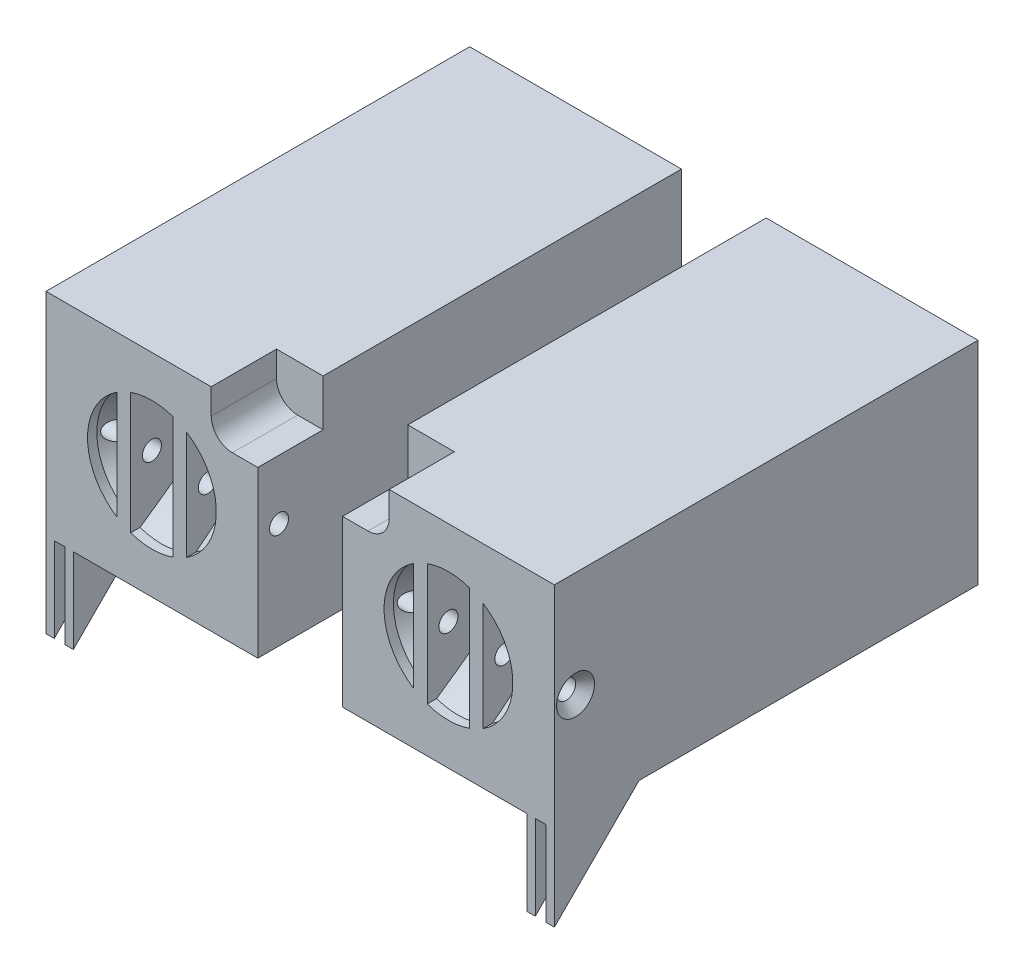
SolidWorks part; units mm, degrees
ref_plane "Alzado" through (0, 0, 0) normal (0, 0, 1) x (1, 0, 0)
ref_plane "Planta" through (0, 0, 0) normal (0, 1, 0) x (1, 0, 0)
ref_plane "Vista lateral" through (0, 0, 0) normal (1, 0, 0) x (0, 0, -1)
sketch "Croquis1" plane through (0, 0, 0) normal (0, 0, 1) x (1, 0, 0)
  line L1 (25, -25) -> (-25, -25)
  line L2 (25, -25) -> (25, 25)
  line L3 (25, 25) -> (-25, 25)
  line L4 (-25, -25) -> (-25, 25)
  line L5 (25, -25) -> (-25, 25) construction
  line L6 (25, 25) -> (-25, -25) construction
  circle A0 centre (0, 0) radius 2
  point P0 (0, 0)
  dimension "D3" = 4
  dimension "D1" = 50
  dimension "D2" = 50
extrude "Saliente-Extruir2" add sketch "Croquis1" along normal blind 100
ref_plane "Plano1" through (0, 0, 0) normal (1, 0, 0) x (0, 0, -1)
sketch "Croquis2" plane through (0, 0, 0) normal (1, 0, 0) x (0, 0, -1)
  line L1 (-100, 25) -> (-100, -25) construction
  line L4 (-100, 15.2) -> (-100, 0)
  line L6 (-97.8, 15.2) -> (-89.8, 10)
  line L7 (-100, 15.2) -> (-97.8, 15.2)
  line L8 (-89.8, 0) -> (-89.8, 10)
  line L9 (-100, 0) -> (-89.8, 0)
  dimension "D1" = 2.2
  dimension "D2" = 10.2
  dimension "D3" = 10
  dimension "D4" = 15.2
revolve "Cortar-Revolución1" cut sketch "Croquis2" angle 360 about L9
sketch "Croquis4" plane through (0, 0, 100) normal (0, 0, 1) x (1, 0, 0)
  line L0 (0, -0.44) -> (0, 0.44) construction
  line L1 (-8.2, 20) -> (-5, 20)
  line L2 (-8.2, 20) -> (-8.2, -20)
  line L3 (-8.2, -20) -> (-5, -20)
  line L4 (-5, 20) -> (-5, -20)
  line L5 (8.2, -20) -> (5, -20)
  line L6 (5, 20) -> (5, -20)
  line L7 (8.2, 20) -> (5, 20)
  line L8 (8.2, 20) -> (8.2, -20)
  point P6 (-5, 0)
  dimension "D1" = 3.2
  dimension "D2" = 5
  dimension "D3" = 40
extrude "Saliente-Extruir5" add sketch "Croquis4" along direction (0, 0, 1) on the side against the normal up to surface (10.2 mm away) up to face at (0, -2, 89.8)
sketch "Croquis8" plane through (0, 0, 89.8) normal (0, 0, 1) x (1, 0, 0)
  circle A0 centre (0, 0) radius 4
  dimension "D1" = 8
extrude "Cortar-Extruir3" cut sketch "Croquis8" against normal offset from surface (87.4 mm away) 2.4 up to face at (0, 0, 0)
sketch "Croquis7" plane through (-25, 0, 0) normal (-1, 0, 0) x (0, 0, 1)
  line L1 (100, 25) -> (100, -25) construction
  circle A0 centre (95, 0) radius 2
  dimension "D1" = 4
  dimension "D2" = 5
extrude "Cortar-Extruir2" cut sketch "Croquis7" against normal up to vertex (50 mm away) up to point (25, -25, 100)
hole_wizard "Refrentado para tornillo tapón con cabeza plana de clavija de M41" positions "Croquis10" profile "Croquis11" countersink size "M4" standard "Ansi Metric" end condition through all
sketch "Croquis10" plane through (-25, 0, 0) normal (-1, 0, 0) x (0, 0, 1)
  point P0 (95, 0)
sketch "Croquis11" plane through (-25, 0, 95) normal (0, 1, 0) x (0, 0, 1)
  line L0 (0, 0) -> (0, 50)
  line L1 (0, 50) -> (2.25, 50)
  line L2 (2.25, 50) -> (2.25, 2.23)
  line L3 (2.25, 2.23) -> (4.48, 0)
  line L5 (4.48, 0) -> (0, 0)
  line L6 (-2.25, 2.23) -> (-4.48, 0) construction
  line L11 (0, -6.35) -> (0, 107.95) construction
  dimension "Diámetro de taladro hasta el siguiente" = 4.5
  dimension "Profundidad de taladro hasta el siguiente" = 50
  dimension "Diámetro de avellanado cercano" = 8.96
  dimension "Ángulo de avellanado cercano" = 90
sketch "Croquis12" plane through (-25, 0, 0) normal (-1, 0, 0) x (0, 0, 1)
  line L1 (100, -25) -> (80, -25)
  line L2 (100, 0) -> (0, 0) construction
  line L5 (100, 25) -> (100, -25) construction
  line L6 (0, 25) -> (0, -25) construction
  line L10 (100, -25) -> (100, -45)
  line L11 (100, -45) -> (80, -25)
extrude "Saliente-Extruir6" add sketch "Croquis12" against normal blind 1.95
extrude "Saliente-Extruir7" add sketch "Croquis12<2>" against normal blind 1.95 from offset 4.5 offset against normal yes
sketch "Croquis12<2>" plane through (-25, 0, 0) normal (-1, 0, 0) x (0, 0, 1) same geometry as "Croquis12"
sketch "Croquis13" plane through (0, 0, 100) normal (0, 0, 1) x (1, 0, 0)
  line L0 (25, 25) -> (25, 14)
  line L1 (25, -25) -> (25, 25) construction
  line L2 (25, 14) -> (19, 14)
  line L3 (14, 19) -> (14, 25)
  line L4 (25, 25) -> (-25, 25) construction
  line L5 (14, 25) -> (25, 25)
  line L6 (25, 25) -> (19.8028, 19.8028) construction
  arc A0 (19, 14) -> (14, 19) centre (19, 19) cw
  dimension "D3" = 5
  dimension "D1" = 11
  dimension "D2" = 11
  dimension "D4" = 45
  dimension "D5" = 7.35
extrude "Cortar-Extruir4" cut sketch "Croquis13" against normal blind 15.4
ref_plane "Plano2" through (35, 0, 0) normal (1, 0, 0) x (0, 0, -1)
mirror "Simetría3" about plane through (35, 0, 0) normal (1, 0, 0) of bodies 118
